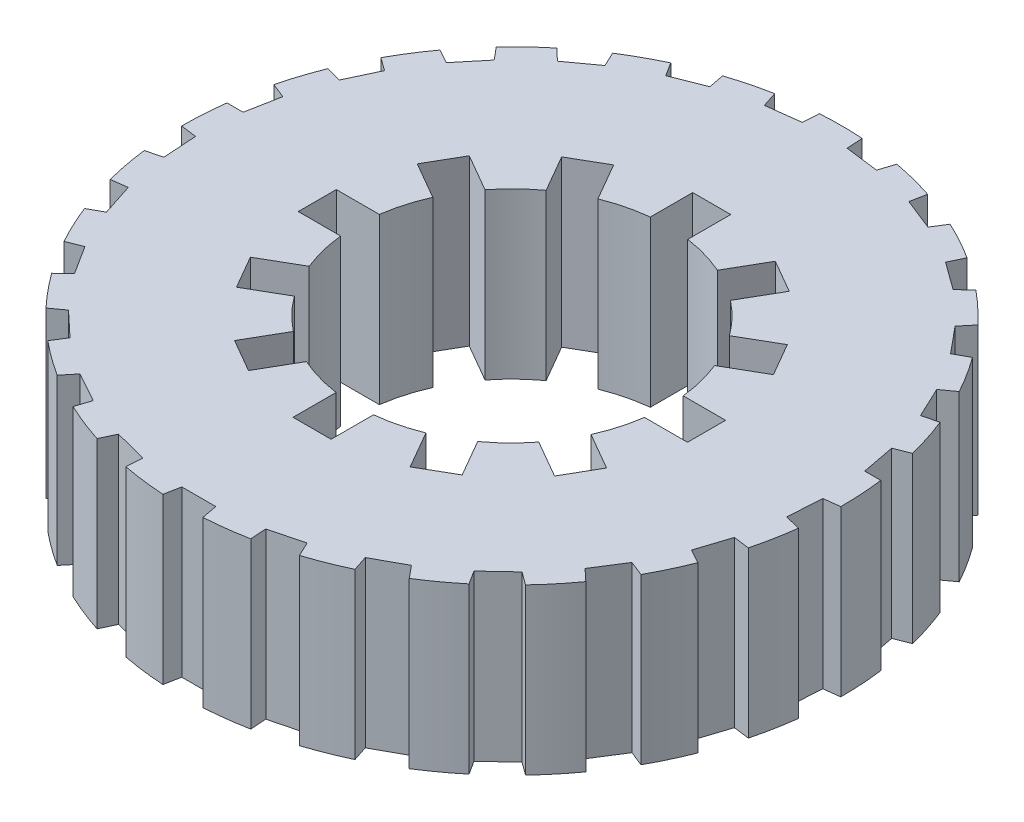
SolidWorks part; units mm, degrees
ref_plane "Front Plane" through (0, 0, 0) normal (0, 0, 1) x (1, 0, 0)
ref_plane "Top Plane" through (0, 0, 0) normal (0, 1, 0) x (1, 0, 0)
ref_plane "Right Plane" through (0, 0, 0) normal (1, 0, 0) x (0, 0, -1)
sketch "Sketch1" plane through (0, 0, 0) normal (0, 1, 0) x (1, 0, 0)
  circle A0 centre (0, 0) radius 38.1
extrude "Boss-Extrude1" add sketch "Sketch1" along normal blind 19.05
sketch "Sketch2" plane through (0, 0, 0) normal (0, -1, 0) x (1, 0, 0)
  line L6 (-1.9657, 36.2) -> (1.9657, 36.2)
  line L7 (2.3241, 38.105) -> (1.9657, 36.2)
  line L8 (-2.3241, 38.105) -> (-1.9657, 36.2)
  line L9 (-2.3241, 38.105) -> (2.3241, 38.105)
  dimension "D1" = 1.905
  dimension "D2" = 36.2
extrude "Cut-Extrude1" cut sketch "Sketch2" against normal blind 33
pattern_circular "CirPattern1" count 25 over 360 about axis through (0, 0, 0) along (0, 1, 0) of "Cut-Extrude1"
sketch "Sketch3" plane through (0, 19.05, 0) normal (0, 1, 0) x (1, 0, 0)
  line L16 (-1.9, 22.8) -> (-1.9, 17.8994)
  line L17 (0.3, 22.8) -> (-1.9, 22.8)
  line L18 (0.3, 22.8) -> (2.5, 22.8)
  line L19 (2.5, 22.8) -> (2.5, 17.8255)
  circle A1 centre (0, 0) radius 18
extrude "Cut-Extrude2" cut sketch "Sketch3" against normal blind 28 contours A1 region at (0, 19.05, 0)
extrude "Cut-Extrude8" cut sketch "Sketch3<7>" against normal blind 23 contours A1 region at (0.3056, 19.05, -20.3761)
sketch "Sketch3<7>" plane through (0, 19.05, 0) normal (0, 1, 0) x (1, 0, 0) same geometry as "Sketch3"
pattern_circular "CirPattern2" count 12 every 30 about axis through (0, 19.05, 0) along (0, 1, 0) of "Cut-Extrude8"
